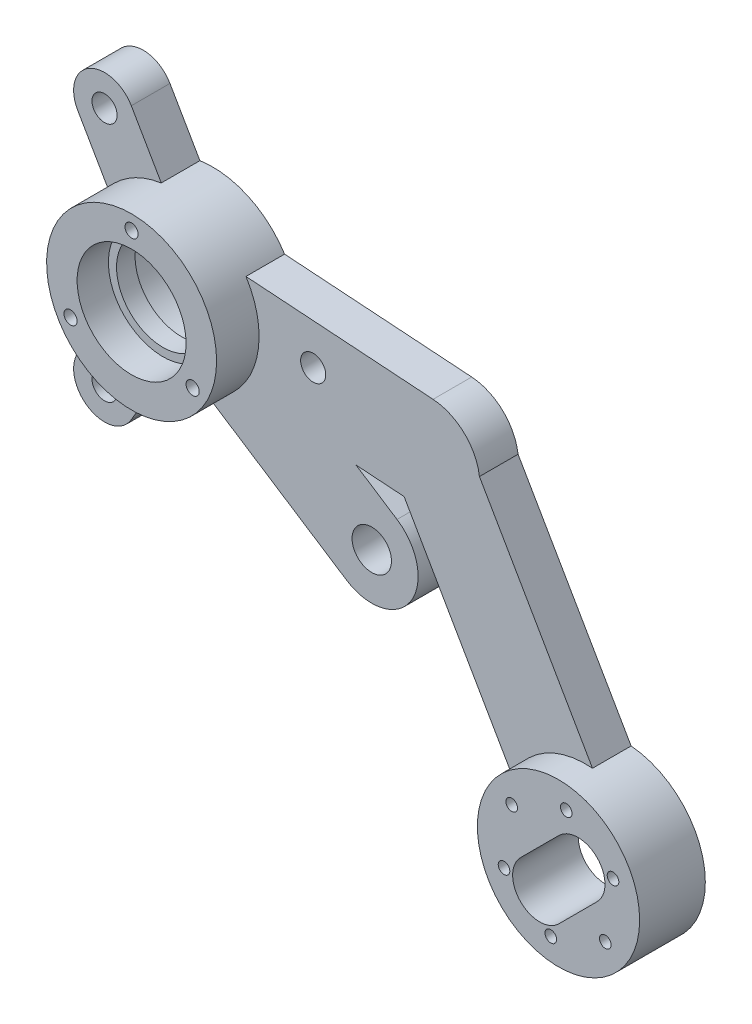
SolidWorks part; units mm, degrees
ref_plane "Front Plane" through (0, 0, 0) normal (0, 0, 1) x (1, 0, 0)
ref_plane "Top Plane" through (0, 0, 0) normal (0, 1, 0) x (1, 0, 0)
ref_plane "Right Plane" through (0, 0, 0) normal (1, 0, 0) x (0, 0, -1)
sketch "S01 - Bearing barrel" plane through (0, 0, 0) normal (0, 0, 1) x (1, 0, 0)
  circle A0 centre (0, 0) radius 22
  dimension "D1" = 44
extrude "01 - Bearing barrel" add sketch "S01 - Bearing barrel" along normal blind 21
sketch "S02 - Torque arm 1" plane through (0, 0, 0) normal (0, 0, 1) x (1, 0, 0)
  line L0 (0, 8) -> (36, 8)
  line L1 (36, -8) -> (0, -8)
  arc A0 (36, 8) -> (36, -8) centre (36, 0) cw
  arc A1 (0, -8) -> (0, 8) centre (0, 0) cw
  dimension "D1" = 8
  dimension "D2" = 36
extrude "02 - Torque arm 1" add sketch "S02 - Torque arm 1" along normal blind 10
sketch "S03 - Torque arm 2" plane through (0, 0, 0) normal (0, 0, 1) x (1, 0, 0)
  line L0 (-6.9282, -4) -> (-24.9282, 27.1769)
  line L1 (-11.0718, 35.1769) -> (6.9282, 4)
  arc A0 (-24.9282, 27.1769) -> (-11.0718, 35.1769) centre (-18, 31.1769) cw
  arc A1 (6.9282, 4) -> (-6.9282, -4) centre (0, 0) cw
  dimension "D1" = 8
  dimension "D2" = 8
  dimension "D3" = 6.9282
  dimension "D4" = 6.9282
  dimension "D5" = 11.0718
  dimension "D6" = 18
  dimension "D7" = 24.9282
  dimension "D8" = 27.1769
extrude "03 - Torque arm 2" add sketch "S03 - Torque arm 2" along normal blind 10
sketch "S04 - Torque arm 3" plane through (0, 0, 0) normal (0, 0, 1) x (1, 0, 0)
  line L0 (6.9282, -4) -> (-11.0718, -35.1769)
  line L1 (-24.9282, -27.1769) -> (-6.9282, 4)
  arc A0 (-11.0718, -35.1769) -> (-24.9282, -27.1769) centre (-18, -31.1769) cw
  arc A1 (-6.9282, 4) -> (6.9282, -4) centre (0, 0) cw
  dimension "D1" = 8
  dimension "D2" = 8
  dimension "D3" = 6.9282
  dimension "D4" = 6.9282
  dimension "D5" = 11.0718
  dimension "D6" = 18
  dimension "D7" = 24.9282
  dimension "D8" = 27.1769
extrude "04 - Torque arm 3" add sketch "S04 - Torque arm 3" along normal blind 10
sketch "S05 - Wheel arm root to rounded elbow" plane through (0, 0, 0) normal (0, 0, 1) x (1, 0, 0)
  line L0 (0.8909, 12.9694) -> (67.0223, 8.4265)
  line L1 (65.2405, -17.5124) -> (-0.8909, -12.9694)
  arc A0 (67.0223, 8.4265) -> (65.2405, -17.5124) centre (66.1314, -4.5429) cw
  arc A1 (-0.8909, -12.9694) -> (0.8909, 12.9694) centre (0, 0) cw
  dimension "D1" = 13
  dimension "D2" = 13
  dimension "D3" = 0.8909
  dimension "D4" = 65.2405
  dimension "D5" = 66.1314
  dimension "D6" = 67.0223
  dimension "D7" = 0.8909
  dimension "D8" = 8.4265
extrude "05 - Wheel arm root to rounded elbow" add sketch "S05 - Wheel arm root to rounded elbow" along normal blind 10
sketch "S06 - Long dropped wheel arm" plane through (0, 0, 0) normal (0, 0, 1) x (1, 0, 0)
  line L0 (76.5281, 1.4494) -> (116.8865, -68.5726)
  line L1 (96.093, -80.5573) -> (55.7347, -10.5353)
  arc A0 (116.8865, -68.5726) -> (96.093, -80.5573) centre (106.4898, -74.5649) cw
  arc A1 (55.7347, -10.5353) -> (76.5281, 1.4494) centre (66.1314, -4.5429) cw
  dimension "D1" = 12
  dimension "D2" = 12
  dimension "D3" = 55.7347
  dimension "D4" = 66.1314
  dimension "D5" = 76.5281
  dimension "D6" = 96.093
  dimension "D7" = 106.4898
  dimension "D8" = 116.8865
  dimension "D9" = 1.4494
  dimension "D10" = 68.5726
extrude "06 - Long dropped wheel arm" add sketch "S06 - Long dropped wheel arm" along normal blind 10
sketch "S07 - Broad cam follower mounting lug" plane through (0, 0, 0) normal (0, 0, 1) x (1, 0, 0)
  line L0 (6.5357, 10.064) -> (57.6946, -23.1589)
  line L1 (44.6232, -43.287) -> (-6.5357, -10.064)
  arc A0 (57.6946, -23.1589) -> (44.6232, -43.287) centre (51.1589, -33.223) cw
  arc A1 (-6.5357, -10.064) -> (6.5357, 10.064) centre (0, 0) cw
  dimension "D1" = 12
  dimension "D2" = 12
  dimension "D3" = 6.5357
  dimension "D4" = 44.6232
  dimension "D5" = 51.1589
  dimension "D6" = 57.6946
  dimension "D7" = 6.5357
  dimension "D8" = 23.1589
extrude "07 - Broad cam follower mounting lug" add sketch "S07 - Broad cam follower mounting lug" along normal blind 10
sketch "S08 - Bearing through relief" plane through (0, 0, 0) normal (0, 0, 1) x (1, 0, 0)
  circle A0 centre (0, 0) radius 12
  dimension "D1" = 24
extrude "08 - Bearing through relief" cut sketch "S08 - Bearing through relief" along normal blind 23 from offset 1 offset against normal yes
sketch "S09 - Inboard 6001 seat" plane through (0, 0, 0) normal (0, 0, 1) x (1, 0, 0)
  circle A0 centre (0, 0) radius 14.1
  dimension "D1" = 28.2
extrude "09 - Inboard 6001 seat" cut sketch "S09 - Inboard 6001 seat" along normal blind 8.2 from offset 0.1 offset against normal yes
sketch "S10 - Outboard 6001 seat" plane through (0, 0, 0) normal (0, 0, 1) x (1, 0, 0)
  circle A0 centre (0, 0) radius 14.1
  dimension "D1" = 28.2
extrude "10 - Outboard 6001 seat" cut sketch "S10 - Outboard 6001 seat" along normal blind 8.2 from offset 12.9
sketch "S11 - Keeper screws" plane through (0, 0, 0) normal (0, 0, 1) x (1, 0, 0)
  circle A0 centre (0, 18.25) radius 1.7
  circle A1 centre (-15.805, -9.125) radius 1.7
  circle A2 centre (15.805, -9.125) radius 1.7
  dimension "D1" = 3.4
  dimension "D2" = 3.4
  dimension "D3" = 3.4
  dimension "D4" = 15.805
  dimension "D5" = 15.805
  dimension "D6" = 18.25
  dimension "D7" = 9.125
extrude "11 - Keeper screws" cut sketch "S11 - Keeper screws" along normal blind 23 from offset 1 offset against normal yes
sketch "S12 - Torque pin retaining stems" plane through (0, 0, 0) normal (0, 0, 1) x (1, 0, 0)
  circle A0 centre (36, 0) radius 3.25
  circle A1 centre (-18, 31.1769) radius 3.25
  circle A2 centre (-18, -31.1769) radius 3.25
  dimension "D1" = 6.5
  dimension "D2" = 6.5
  dimension "D3" = 6.5
  dimension "D4" = 36
  dimension "D5" = 18
  dimension "D6" = 31.1769
  dimension "D7" = 31.1769
extrude "12 - Torque pin retaining stems" cut sketch "S12 - Torque pin retaining stems" along normal blind 12 from offset 1 offset against normal yes
sketch "S13 - Wheel tip through-bolt land" plane through (0, 0, 0) normal (0, 0, 1) x (1, 0, 0)
  circle A0 centre (106.4898, -74.5649) radius 21
  dimension "D1" = 42
  dimension "D2" = 106.4898
  dimension "D3" = 74.5649
extrude "13 - Wheel tip through-bolt land" add sketch "S13 - Wheel tip through-bolt land" along normal blind 10
sketch "S14 - Inboard 6808 inner-race shoulder" plane through (0, 0, 0) normal (0, 0, 1) x (1, 0, 0)
  circle A0 centre (106.4898, -74.5649) radius 21
  dimension "D1" = 42
  dimension "D2" = 106.4898
  dimension "D3" = 74.5649
extrude "14 - Inboard 6808 inner-race shoulder" add sketch "S14 - Inboard 6808 inner-race shoulder" along normal blind 7 from offset 10
sketch "S19 - Through bore for steel follower bush" plane through (0, 0, 0) normal (0, 0, 1) x (1, 0, 0)
  circle A0 centre (51.1589, -33.223) radius 5.1
  dimension "D1" = 10.2
  dimension "D2" = 51.1589
  dimension "D3" = 33.223
extrude "19 - Through bore for steel follower bush" cut sketch "S19 - Through bore for steel follower bush" along normal blind 12 from offset 1 offset against normal yes
sketch "S20 - Flush seat for bush flange" plane through (0, 0, 0) normal (0, 0, 1) x (1, 0, 0)
  circle A0 centre (51.1589, -33.223) radius 7.6
  dimension "D1" = 15.2
  dimension "D2" = 51.1589
  dimension "D3" = 33.223
extrude "20 - Flush seat for bush flange" cut sketch "S20 - Flush seat for bush flange" along normal blind 2.1 from offset 0.1 offset against normal yes
sketch "Sketch2" plane through (0, 0, 0) normal (0, 0, -1) x (-1, 0, 0)
  circle A3 centre (-104.4936, -89.6989) radius 1.5
  circle A4 centre (-92.3853, -80.4032) radius 1.5
  circle A5 centre (-118.5981, -83.8606) radius 1.5
  circle A6 centre (-120.5942, -68.7267) radius 1.5
  circle A7 centre (-108.4859, -59.431) radius 1.5
  circle A8 centre (-94.3815, -65.2693) radius 1.5
  dimension "D1" = 3
  dimension "D2" = 3
extrude "Cut-Extrude1" cut sketch "Sketch2" against normal through all
sketch "Sketch7" plane through (0, 0, 17) normal (0, 0, 1) x (1, 0, 0)
  line L2 (96.6684, -75.9608) -> (106.5679, -66.0613)
  line L4 (116.4674, -75.9608) -> (106.5679, -85.8603)
  arc A0 (96.6684, -75.9608) -> (106.5679, -85.8603) centre (101.6181, -80.9106) ccw
  arc A1 (116.4674, -75.9608) -> (106.5679, -66.0613) centre (111.5176, -71.0111) ccw
  point P5 (101.6181, -71.0111)
  dimension "D1" = 14
  dimension "D2" = 14
  dimension "D4" = 7
  dimension "D5" = 14
extrude "Cut-Extrude2" cut sketch "Sketch7" against normal through all
